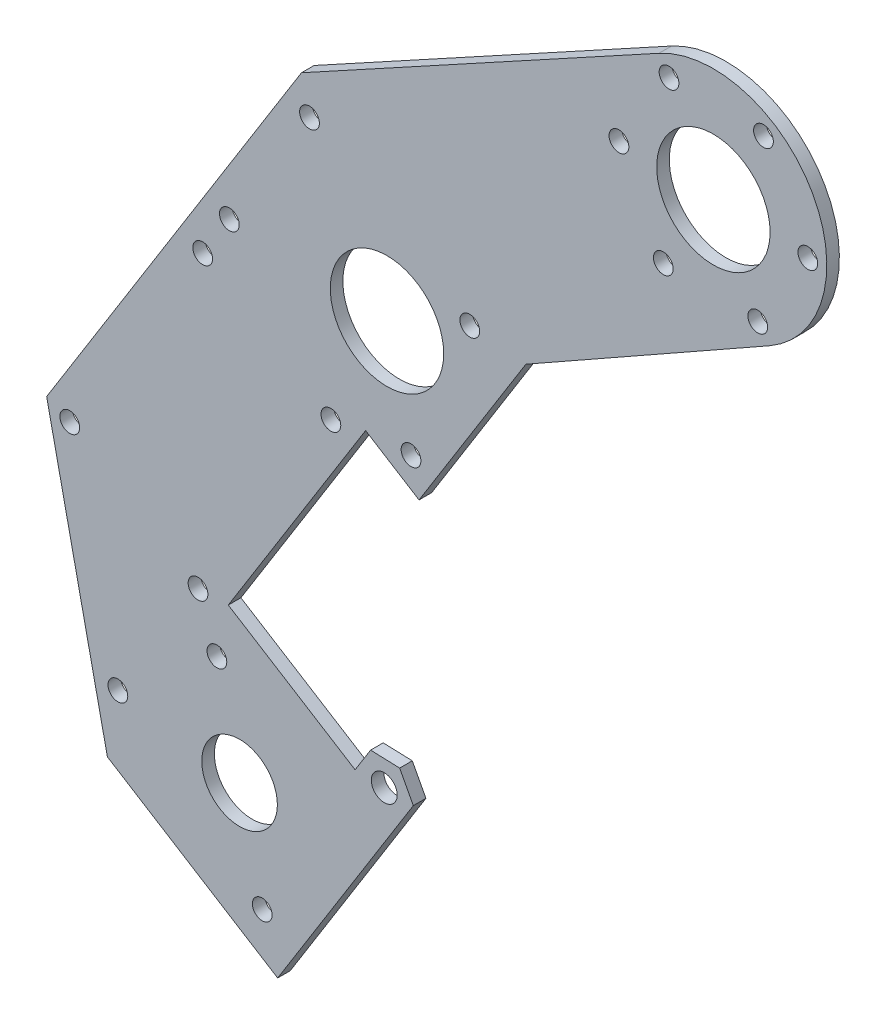
SolidWorks part; units mm, degrees
material "6061 Alloy"
ref_plane "Front Plane" through (0, 0, 0) normal (0, 0, 1) x (1, 0, 0)
ref_plane "Top Plane" through (0, 0, 0) normal (0, 1, 0) x (1, 0, 0)
ref_plane "Right Plane" through (0, 0, 0) normal (1, 0, 0) x (0, 0, -1)
sketch "Sketch1" plane through (0, 0, -14.1946) normal (0, 0, 1) x (1, 0, 0)
  line L0 (-11.4036, 461.0409) -> (18.8813, 509.5069)
  line L1 (-54.3079, 487.8505) -> (-69.6155, 558.824)
  line L2 (8.1111, 516.2368) -> (-23.8465, 536.2061)
  line L3 (10.7592, 591.5868) -> (-157.4902, 322.3315) construction
  line L4 (-11.4036, 461.0409) -> (-54.3079, 487.8505)
  line L5 (-69.6155, 558.824) -> (-5.4017, 661.5875)
  line L6 (-23.8465, 536.2061) -> (10.7592, 591.5868)
  line L8 (-115.7964, 730.5698) -> (48.4493, 627.9377) construction
  line L9 (-142.7163, 687.4889) -> (24.222, 583.1743) construction
  line L10 (51.1419, 626.2552) -> (112.462, 660.9373)
  line L11 (10.7592, 591.5868) -> (24.222, 583.1743)
  line L13 (24.222, 583.1743) -> (51.1419, 626.2552)
  line L16 (-5.4017, 661.5875) -> (84.678, 710.8773)
  line L17 (16.1415, 618.1747) -> (-107.7159, 695.5694) construction
  line L18 (18.8813, 509.5069) -> (22.7847, 515.7536)
  line L19 (-23.8465, 536.2061) -> (-52.9124, 489.691) construction
  line L20 (-4.9986, 524.4287) -> (-34.0645, 477.9135) construction
  line L22 (12.0145, 522.4836) -> (8.1111, 516.2368)
  line L23 (12.0145, 522.4836) -> (19.3423, 522.2277)
  line L24 (19.3423, 522.2277) -> (22.7847, 515.7536)
  line L25 (17.3996, 519.1186) -> (21.0569, 524.9715) construction
  circle A2 centre (16.1415, 618.1747) radius 14.2875
  circle A5 centre (98.3945, 685.8096) radius 14.2875
  arc A7 (112.462, 660.9373) -> (84.678, 710.8773) centre (98.3945, 685.8096) ccw
  circle A8 centre (-107.7159, 695.5694) radius 215.011 construction
  circle A9 centre (-21.0004, 498.8205) radius 9.525
  point P33 (98.3945, 685.8096)
  dimension "D1" = 22.225
  dimension "D2" = 19.05
  dimension "D3" = 7.366
  dimension "D4" = 120
extrude "Boss-Extrude1" add sketch "Sketch1" along normal blind 3.175
sketch "Sketch17" plane through (0, 0, -11.0196) normal (0, 0, 1) x (1, 0, 0)
  line L0 (-4.9986, 524.4287) -> (-34.0645, 477.9135) construction
  line L2 (16.1415, 618.1747) -> (37.6819, 604.7147) construction
  line L11 (-26.7141, 523.5695) -> (-15.2866, 474.0715) construction
  line L12 (24.222, 583.1743) -> (51.1419, 626.2552) construction
  line L13 (37.6819, 604.7147) -> (27.587, 588.5594) construction
  line L14 (27.587, 588.5594) -> (22.2019, 591.9244) construction
  line L15 (22.2019, 591.9244) -> (-28.9566, 623.8918) construction
  line L16 (-5.4017, 661.5875) -> (-69.6155, 558.824) construction
  line L17 (-28.9566, 623.8918) -> (-23.5715, 620.5268) construction
  line L18 (-23.5715, 620.5268) -> (-3.3816, 652.8374) construction
  line L19 (-3.3816, 652.8374) -> (37.0067, 627.6) construction
  line L20 (10.7592, 591.5868) -> (5.3741, 594.9518) construction
  line L21 (5.3741, 594.9518) -> (-31.4748, 535.9811) construction
  line L22 (-31.4748, 535.9811) -> (-51.6648, 503.6705) construction
  line L23 (5.3741, 594.9518) -> (2.0091, 589.5667) construction
  line L24 (-31.4748, 535.9811) -> (-63.7855, 556.1711) construction
  line L25 (2.0091, 589.5667) -> (-30.3015, 609.7566) construction
  circle A1 centre (-21.0004, 498.8205) radius 25.4 construction
  circle A2 centre (15.4568, 516.0095) radius 6.35 construction
  point P32 (-21.0004, 498.8205)
  dimension "D1" = 45
hole_wizard "#10 Clearance Hole2" positions "Sketch20" profile "Sketch21" hole size "#10" standard "ANSI Inch" end condition through all
sketch "Sketch20" plane through (0, 0, -11.0196) normal (0, 0, 1) x (1, 0, 0)
  point P0 (-26.7141, 523.5695)
  point P3 (-15.2866, 474.0715)
  point P24 (-3.3816, 652.8374)
  point P27 (37.0067, 627.6)
  point P30 (22.2019, 591.9244)
  point P33 (-23.5715, 620.5268)
  point P42 (-31.4748, 535.9811)
  point P45 (-63.7855, 556.1711)
  point P48 (-51.6648, 503.6705)
  point P54 (2.0091, 589.5667)
  point P57 (-30.3015, 609.7566)
sketch "Sketch21" plane through (-26.7141, 523.5695, -11.0196) normal (1, 0, 0) x (0, -1, 0)
  line L0 (0, 0) -> (0, 3.175)
  line L1 (0, 3.175) -> (2.4892, 3.175)
  line L2 (2.4892, 3.175) -> (2.4892, 0)
  line L5 (2.4892, 0) -> (0, 0)
  line L11 (0, -6.35) -> (0, 107.95) construction
  dimension "Thru Hole Dia." = 4.9784
  dimension "Thru Hole Depth" = 3.175
sketch "Sketch22" plane through (0, 0, -11.0196) normal (0, 0, 1) x (1, 0, 0)
  line L0 (98.3945, 685.8096) -> (111.0132, 706.0038) construction
  line L2 (111.0132, 706.0038) -> (87.2152, 706.8348) construction
  line L3 (87.2152, 706.8348) -> (74.5965, 686.6407) construction
  line L4 (74.5965, 686.6407) -> (85.7758, 665.6155) construction
  line L5 (85.7758, 665.6155) -> (109.5738, 664.7845) construction
  line L6 (109.5738, 664.7845) -> (122.1925, 684.9786) construction
  line L7 (122.1925, 684.9786) -> (111.0132, 706.0038) construction
  circle A0 centre (98.3945, 685.8096) radius 23.8125 construction
hole_wizard "#10 Clearance Hole3" positions "Sketch23" profile "Sketch24" hole size "#10" standard "ANSI Inch" end condition through all
sketch "Sketch23" plane through (0, 0, -11.0196) normal (0, 0, 1) x (1, 0, 0)
  point P0 (111.0132, 706.0038)
  point P3 (122.1925, 684.9786)
  point P6 (109.5738, 664.7845)
  point P9 (85.7758, 665.6155)
  point P12 (74.5965, 686.6407)
  point P15 (87.2152, 706.8348)
sketch "Sketch24" plane through (111.0132, 706.0038, -11.0196) normal (1, 0, 0) x (0, -1, 0)
  line L0 (0, 0) -> (0, 3.175)
  line L1 (0, 3.175) -> (2.4892, 3.175)
  line L2 (2.4892, 3.175) -> (2.4892, 0)
  line L5 (2.4892, 0) -> (0, 0)
  line L11 (0, -6.35) -> (0, 107.95) construction
  dimension "Thru Hole Dia." = 4.9784
  dimension "Thru Hole Depth" = 3.175
hole_wizard "1/4 Clearance Hole1" positions "Sketch25" profile "Sketch26" hole size "1/4" standard "ANSI Inch" end condition through all
sketch "Sketch25" plane through (0, 0, -11.0196) normal (0, 0, 1) x (1, 0, 0)
  point P0 (15.4568, 516.0095)
sketch "Sketch26" plane through (15.4568, 516.0095, -11.0196) normal (1, 0, 0) x (0, -1, 0)
  line L0 (0, 0) -> (0, 3.175)
  line L1 (0, 3.175) -> (3.2639, 3.175)
  line L2 (3.2639, 3.175) -> (3.2639, 0)
  line L5 (3.2639, 0) -> (0, 0)
  line L11 (0, -6.35) -> (0, 107.95) construction
  dimension "Thru Hole Dia." = 6.5278
  dimension "Thru Hole Depth" = 3.175
